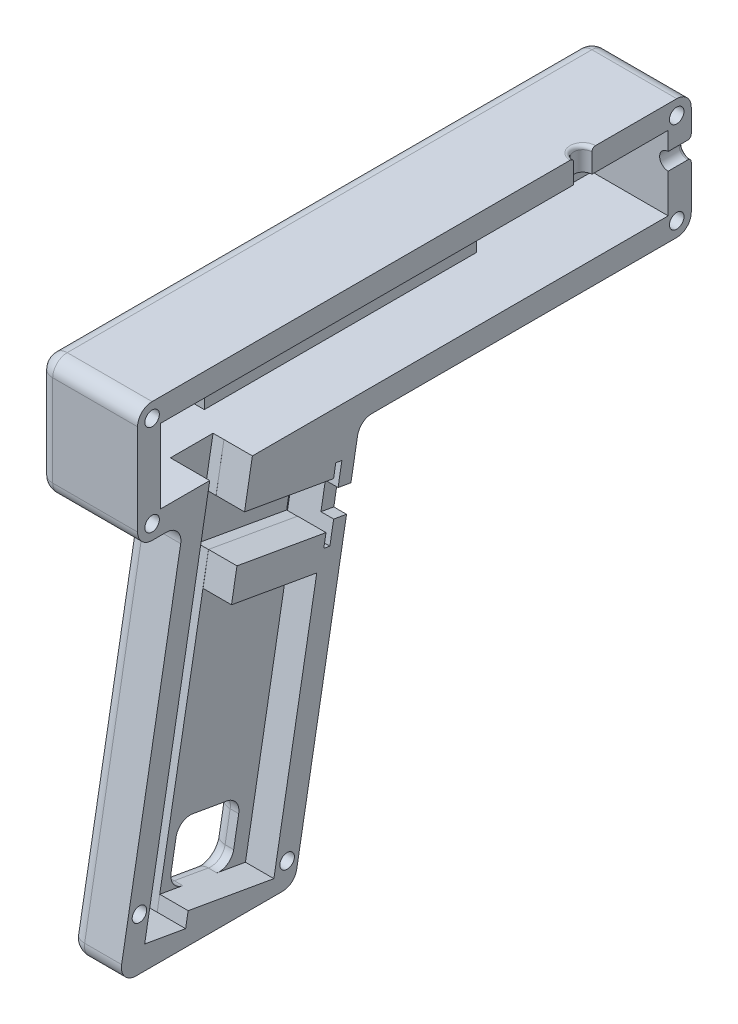
SolidWorks part; units mm, degrees
ref_plane "Front Plane" through (0, 0, 0) normal (0, 0, 1) x (1, 0, 0)
ref_plane "Top Plane" through (0, 0, 0) normal (0, 1, 0) x (1, 0, 0)
ref_plane "Right Plane" through (0, 0, 0) normal (1, 0, 0) x (0, 0, -1)
sketch "Sketch1" plane through (0, 0, 0) normal (0, 0, 1) x (1, 0, 0)
  line L1 (0, 0) -> (27.35, 0)
  line L2 (0, 0) -> (0, 33.1)
  line L3 (0, 33.1) -> (27.35, 33.1)
  line L4 (27.35, 0) -> (27.35, 33.1)
  dimension "D1" = 33.1
  dimension "D2" = 27.35
extrude "Boss-Extrude1" add sketch "Sketch1" against normal blind 152.4
sketch "Sketch2" plane through (27.35, 0, 0) normal (1, 0, 0) x (0, 0, -1)
  line L0 (0, 0) -> (0, 33.1) construction
  line L1 (6.35, 26.75) -> (146.05, 26.75)
  line L2 (6.35, 26.75) -> (6.35, 6.35)
  line L3 (6.35, 6.35) -> (146.05, 6.35)
  line L4 (146.05, 26.75) -> (146.05, 6.35)
  line L5 (152.4, 33.1) -> (0, 33.1) construction
  line L6 (152.4, 0) -> (0, 0) construction
  line L7 (152.4, 0) -> (152.4, 33.1) construction
  point P12 (6.35, 16.55)
  point P13 (0, 16.55)
  dimension "D1" = 6.35
  dimension "D2" = 6.35
  dimension "D3" = 6.35
  dimension "D4" = 6.35
extrude "Cut-Extrude1" cut sketch "Sketch2" against normal blind 21
sketch "Sketch4" plane through (0, 33.1, 0) normal (0, 1, 0) x (1, 0, 0)
  line L0 (27.35, 152.4) -> (27.35, 0) construction
  line L2 (27.35, 120.055) -> (27.35, 125.055)
  line L3 (27.35, 152.4) -> (0, 152.4) construction
  arc A2 (27.35, 120.055) -> (27.35, 125.055) centre (27.35, 122.555) cw
  dimension "D1" = 29.845
sketch "Sketch5" plane through (6.35, 0, 0) normal (1, 0, 0) x (0, 0, -1)
  line L0 (33.02, 17.4) -> (107.95, 17.4)
  line L1 (33.02, 23.75) -> (107.95, 23.75)
  line L2 (33.02, 23.75) -> (33.02, 9.35)
  line L3 (33.02, 9.35) -> (107.95, 9.35)
  line L4 (107.95, 23.75) -> (107.95, 9.35)
  line L9 (33.02, 15.7) -> (107.95, 15.7)
  line L10 (6.35, 6.35) -> (146.05, 6.35) construction
  line L11 (146.05, 6.35) -> (146.05, 26.75) construction
  line M13 (146.05, 6.35) -> (146.05, 26.75)
  dimension "D1" = 1.7
  dimension "D2" = 6.35
  dimension "D3" = 6.35
  dimension "D4" = 3
  dimension "D5" = 38.1
  dimension "D6" = 74.93
extrude "PCB Slot" add sketch "Sketch5" along normal blind 6.35 contours L1 L2 L0 M13 | L9 L2 L3 M13 region at (6.35, 20.575, -70.485) region at (6.35, 12.525, -70.485)
sketch "Sketch8" plane through (27.35, 0, 25.4) normal (1, 0, 0) x (0, 0, -1)
  line L0 (38.1, 0) -> (20.1852, -101.6)
  line L1 (20.1852, -101.6) -> (68.621, -101.6)
  line L2 (68.621, -101.6) -> (86.5358, 0)
  line L4 (38.1, 0) -> (86.5358, 0)
  dimension "D1" = 12.7
  dimension "D3" = 47.7
extrude "Butt" add sketch "Sketch8" against normal blind 14.175
sketch "Sketch9" plane through (27.35, 0, 25.4) normal (1, 0, 0) x (0, 0, -1)
  line L7 (68.621, -101.6) -> (86.5358, 0) construction
  line L8 (51.2564, -26.2652) -> (74.7269, -30.4036)
  line L9 (28.0575, -91.2236) -> (62.9188, -97.3706)
  line L10 (74.7269, -30.4036) -> (62.9188, -97.3706)
  line L12 (31.75, 6.35) -> (171.45, 6.35) construction
  line L13 (45.2623, 6.35) -> (57.0073, 6.35)
  line L14 (57.0073, 6.35) -> (51.2564, -26.2652)
  line L15 (45.2623, 6.35) -> (28.0575, -91.2236)
  dimension "D3" = 68
  dimension "D4" = 3.175
extrude "BatteryPack" cut sketch "Sketch9" against normal blind 7.825
sketch "Sketch10" plane through (19.525, 0, 0) normal (1, 0, 0) x (0, 0, -1)
  line L0 (33.5796, -96.676) -> (16.3455, -93.6371)
  line L2 (16.3455, -93.6371) -> (19.1238, -77.8802)
  line L3 (36.358, -80.9191) -> (19.1238, -77.8802)
  line L4 (2.6575, -91.2236) -> (37.5188, -97.3706) construction
  line L5 (36.358, -80.9191) -> (33.5796, -96.676)
  dimension "D1" = 16
extrude "BatterySwitch" cut sketch "Sketch10" against normal up to next
sketch "Sketch11" plane through (0, -88.0184, 15.52) normal (0, 0.9848, -0.1736) x (1, 0, 0)
  line L0 (19.525, 18.4579) -> (27.35, 18.4579)
  line L1 (19.525, 18.4579) -> (19.525, 29.8992)
  line L2 (27.35, 18.4579) -> (27.35, 29.8992)
  line L3 (19.525, 29.8992) -> (27.35, 29.8992)
  dimension "D1" = 11.4413
extrude "WireSpace" cut sketch "Sketch11" against normal blind 4
sketch "Sketch12" plane through (19.525, 0, 0) normal (1, 0, 0) x (0, 0, -1)
  line L0 (19.8623, 6.35) -> (31.6073, 6.35)
  line L1 (31.6073, 6.35) -> (13.2303, -97.1496)
  line L2 (13.2303, -97.1496) -> (1.9629, -95.1628)
  line L3 (1.9629, -95.1628) -> (19.8623, 6.35)
extrude "WireRoute" cut sketch "Sketch12" against normal blind 3
sketch "Sketch13" plane through (27.35, 0, 0) normal (1, 0, 0) x (0, 0, -1)
  line L0 (152.4, 33.1) -> (0, 33.1) construction
  line L1 (0, 0) -> (0, 33.1) construction
  line L3 (152.4, 0) -> (152.4, 33.1) construction
  line L7 (12.7, 0) -> (0, 0) construction
  line L8 (49.3269, -30.4036) -> (25.8564, -26.2652) construction
  line L9 (43.221, -101.6) -> (61.1358, 0) construction
  line L10 (12.7, 0) -> (-5.2148, -101.6) construction
  circle A0 centre (4, 29.1) radius 2
  circle A1 centre (148.4, 29.1) radius 2
  circle A2 centre (148.4, 4) radius 2
  circle A3 centre (4, 4) radius 2
  circle A5 centre (0.5231, -87.3425) radius 2
  circle A6 centre (41.1665, -94.9675) radius 2
  dimension "D1" = 4
  dimension "D5" = 64.5486
  dimension "D2" = 4
  dimension "D3" = 4
  dimension "D4" = 4
  dimension "D6" = 65
  dimension "D7" = 3.175
  dimension "D8" = 3.175
extrude "PressFit" cut sketch "Sketch13" against normal blind 3.5
extrude "HitLED" cut sketch "Sketch4" against normal up to next
sketch "Sketch15" plane through (0, 0, -146.05) normal (0, 0, 1) x (1, 0, 0)
  line L0 (27.35, 6.35) -> (27.35, 26.75) construction
  line L1 (27.35, 21.7) -> (27.35, 17)
  arc A0 (27.35, 17) -> (27.35, 21.7) centre (27.35, 19.35) cw
  dimension "D1" = 13
  dimension "D2" = 0
extrude "IRLED" cut sketch "Sketch15" against normal up to next
fillet "Fillet-LED's" radius 1 2 edges at (25, 19.35, -152.4) (24.85, 33.1, -122.555)
sketch "Sketch16" plane through (27.35, 0, 0) normal (1, 0, 0) x (0, 0, -1)
  line L0 (55.1893, -12.9928) -> (53.9738, -19.8865)
  line L1 (53.9738, -19.8865) -> (57.5191, -20.5116)
  line L2 (57.5191, -20.5116) -> (58.7346, -13.618)
  line L3 (58.7346, -13.618) -> (55.1893, -12.9928)
  line L4 (43.221, -101.6) -> (61.1358, 0) construction
  line L5 (49.3269, -30.4036) -> (25.8564, -26.2652) construction
  point P9 (56.962, -13.3054)
  dimension "D1" = 7
  dimension "D2" = 3.6
  dimension "D3" = 0
  dimension "D4" = 13.3054
extrude "Trigger" cut sketch "Sketch16" against normal blind 3.5
sketch "Sketch18" plane through (27.35, 0, 0) normal (1, 0, 0) x (0, 0, -1)
  line L0 (54.5614, -6.7642) -> (51.2534, -25.5248)
  line L1 (51.2534, -25.5248) -> (52.9276, -25.82)
  line L2 (52.9276, -25.82) -> (56.2356, -7.0594)
  line L3 (56.2356, -7.0594) -> (54.5614, -6.7642)
  line L4 (55.1893, -12.9928) -> (53.9738, -19.8865) construction
  line L5 (58.7346, -13.618) -> (55.1893, -12.9928) construction
  point P6 (55.3985, -6.9118)
  dimension "D1" = 0
  dimension "D2" = 1.7
  dimension "D3" = 19.05
  dimension "D4" = 6.025
extrude "ButtonPCB" cut sketch "Sketch18" against normal blind 12.065 contours L3 L0 L1 L2
sketch "Sketch20" plane through (27.35, 0, 0) normal (1, 0, 0) x (0, 0, -1)
  line L0 (29.4447, -5.9148) -> (53.9493, -10.2356)
  line L1 (25.8564, -26.2652) -> (31.6073, 6.35) construction
  line L2 (54.5614, -6.7642) -> (51.2534, -25.5248) construction
  line L3 (53.9493, -10.2356) -> (51.8655, -22.0533)
  line L4 (51.8655, -22.0533) -> (27.3609, -17.7325)
  line L5 (27.3609, -17.7325) -> (29.4447, -5.9148)
  line L6 (51.2534, -25.5248) -> (52.9276, -25.82) construction
  line L7 (56.2356, -7.0594) -> (54.5614, -6.7642) construction
  dimension "D1" = 12
  dimension "D2" = 3.525
extrude "ButtonWireSpace" cut sketch "Sketch20" against normal up to vertex (7.825 mm away) up to point (19.525, 6.35, -31.6073)
fillet "Fillet-Body" radius 4 24 edges at (16.35, -96.676, -33.5796) (16.35, -93.6371, -16.3455) (16.35, -77.8802, -19.1238) (16.35, -80.9191, -36.358) (20.2625, -101.6, 5.2148) (13.675, 0, -152.4) (0, 16.55, -152.4) (13.175, -88.7975, -34.9688) (13.175, -79.3996, -27.7409) (13.175, -85.7587, -17.7347) (13.175, -95.1566, -24.9625) (13.175, -101.6, -19.0031) (20.2625, -101.6, -43.221) (13.175, -50.8, -52.1784) (20.2625, 0, -61.1358) (13.175, 0, -36.9179) (0, 0, -76.2) (13.175, -50.8, -3.7426) (20.2625, 0, -12.7) (13.675, 0, 0) (0, 16.55, 0) (13.675, 33.1, -152.4) (0, 33.1, -76.2) (13.675, 33.1, 0)
sketch "Sketch22" plane through (0, -5.2465, -29.5483) normal (0, 0.1748, 0.9846) x (1, 0, 0)
  line L0 (19.525, -0.6762) -> (16.525, -0.6762)
  line L1 (19.525, -89.3405) -> (19.525, 11.7778) construction
  line L2 (16.525, -93.3405) -> (16.525, 11.7778) construction
  line L3 (16.525, 11.7778) -> (19.525, 11.7778) construction
  line L4 (19.525, -12.6762) -> (16.525, -12.6762)
  line L5 (19.525, -0.6762) -> (19.525, -12.6762)
  line L6 (16.525, -0.6762) -> (16.525, -12.6762)
  dimension "D1" = 12.454
  dimension "D2" = 12
extrude "Cut-Extrude2" cut sketch "Sketch22" against normal up to next
